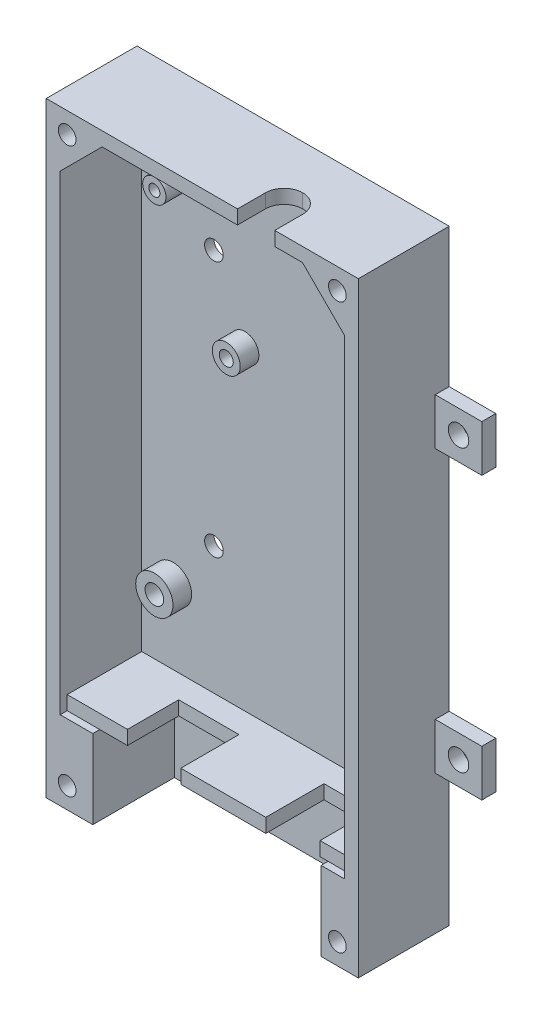
SolidWorks part; units mm, degrees
ref_plane "Front Plane" through (0, 0, 0) normal (0, 0, 1) x (1, 0, 0)
ref_plane "Top Plane" through (0, 0, 0) normal (0, 1, 0) x (1, 0, 0)
ref_plane "Right Plane" through (0, 0, 0) normal (1, 0, 0) x (0, 0, -1)
sketch "Sketch1" plane through (0, 0, 0) normal (0, 0, 1) x (1, 0, 0)
  line L9 (34.9482, -66.4467) -> (-32.0518, -66.4467)
  line L25 (-28.0518, -185.7817) -> (-28.0518, -70.4467) construction
  line L26 (30.9482, -70.4467) -> (-28.0518, -70.4467) construction
  line L27 (30.9482, -185.7817) -> (30.9482, -70.4467) construction
  line L28 (30.9482, -185.7817) -> (-28.0518, -185.7817) construction
  line L29 (15.5804, -174.6788) -> (15.5804, -176.5076)
  line L30 (24.7244, -176.5076) -> (15.5804, -176.5076)
  line L31 (24.7244, -174.6788) -> (24.7244, -176.5076)
  line L32 (24.7244, -174.6788) -> (15.5804, -174.6788)
  line L33 (-15.6108, -174.6788) -> (-15.6108, -181.0288)
  line L34 (-3.6728, -181.0288) -> (-15.6108, -181.0288)
  line L35 (-3.6728, -174.6788) -> (-3.6728, -181.0288)
  line L36 (-3.6728, -174.6788) -> (-15.6108, -174.6788)
  line L37 (-29.0518, -69.4467) -> (-29.0518, -176.5076)
  line L38 (31.9482, -176.5076) -> (-29.0518, -176.5076)
  line L39 (31.9482, -69.4467) -> (31.9482, -176.5076)
  line L40 (31.9482, -69.4467) -> (-29.0518, -69.4467)
  line L41 (31.9482, -179.5076) -> (-29.0518, -179.5076)
  line L42 (34.9482, -196.4467) -> (-32.0518, -196.4467)
  line L43 (-32.0518, -196.4467) -> (-32.0518, -66.4467)
  line L44 (34.9482, -196.4467) -> (34.9482, -66.4467)
  line L45 (31.9482, -186.7817) -> (-29.0518, -186.7817)
  line L46 (-29.0518, -186.7817) -> (-29.0518, -69.4467)
  line L47 (31.9482, -69.4467) -> (-29.0518, -69.4467)
  line L48 (31.9482, -186.7817) -> (31.9482, -69.4467)
  circle A6 centre (25.9944, -160.5564) radius 1.5621
  circle A7 centre (-22.3418, -160.5564) radius 1.5621
  circle A8 centre (-6.9003, -108.9309) radius 1.3153
  circle A9 centre (21.1159, -108.9309) radius 1.5621
  circle A10 centre (-22.3418, -85.4232) radius 1.5621
  circle A11 centre (25.9944, -77.9302) radius 1.5621
extrude "Boss-Extrude1" add sketch "Sketch1" against normal blind 2 contours L9 L43 L42 L44
sketch "Sketch2" plane through (0, 0, 0) normal (0, 0, 1) x (1, 0, 0)
  line L0 (-32.0518, -66.4467) -> (34.9482, -66.4467)
  line L22 (15.0804, -179.5076) -> (-3.1728, -179.5076)
  line L23 (15.0804, -176.5076) -> (15.0804, -179.5076)
  line L24 (-3.1728, -176.5076) -> (15.0804, -176.5076)
  line L25 (-3.1728, -179.5076) -> (-3.1728, -176.5076)
  line L26 (-32.0518, -179.5076) -> (-32.0518, -66.4467)
  line L27 (-16.1108, -179.5076) -> (-32.0518, -179.5076)
  line L28 (-16.1108, -176.5076) -> (-16.1108, -179.5076)
  line L29 (-29.0518, -176.5076) -> (-16.1108, -176.5076)
  line L30 (-29.0518, -69.4467) -> (-29.0518, -176.5076)
  line L31 (31.9482, -69.4467) -> (-29.0518, -69.4467)
  line L32 (31.9482, -176.5076) -> (31.9482, -69.4467)
  line L33 (25.2244, -176.5076) -> (31.9482, -176.5076)
  line L34 (25.2244, -179.5076) -> (25.2244, -176.5076)
  line L35 (34.9482, -179.5076) -> (25.2244, -179.5076)
  line L36 (34.9482, -66.4467) -> (34.9482, -179.5076)
extrude "Boss-Extrude2" add sketch "Sketch2" along normal blind 17.5
sketch "Sketch3" plane through (0, 0, 0) normal (0, 0, 1) x (1, 0, 0)
  circle A10 centre (-6.9003, -108.9309) radius 3
  circle A11 centre (-6.9003, -108.9309) radius 1.5
  circle A12 centre (-22.3418, -85.4232) radius 2.5
  circle A13 centre (-22.3418, -85.4232) radius 1.2
  circle A14 centre (25.9944, -77.9302) radius 2.5
  circle A15 centre (25.9944, -77.9302) radius 1.2
  circle A16 centre (25.9944, -160.5564) radius 2.5
  circle A17 centre (25.9944, -160.5564) radius 1.2
  circle A18 centre (-22.3418, -160.5564) radius 4
  circle A19 centre (-22.3418, -160.5564) radius 2
extrude "Boss-Extrude3" add sketch "Sketch3" along normal blind 4
sketch "Sketch4" plane through (0, 0, 0) normal (0, 0, 1) x (1, 0, 0)
  line L1 (-16.1108, -179.5076) -> (-3.1728, -179.5076)
  line L2 (-16.1108, -179.5076) -> (-16.1108, -176.5076)
  line L3 (-16.1108, -176.5076) -> (-3.1728, -176.5076)
  line L4 (-3.1728, -179.5076) -> (-3.1728, -176.5076)
  line L5 (15.0804, -179.5076) -> (25.2244, -179.5076)
  line L6 (15.0804, -179.5076) -> (15.0804, -176.5076)
  line L7 (15.0804, -176.5076) -> (25.2244, -176.5076)
  line L8 (25.2244, -179.5076) -> (25.2244, -176.5076)
extrude "Boss-Extrude4" add sketch "Sketch4" along normal blind 5
sketch "Sketch5" plane through (0, 0, 0) normal (0, 0, 1) x (1, 0, 0)
  line L7 (-13.5518, -94.1361) -> (16.4482, -94.1361) construction
  line L8 (-13.5518, -94.1361) -> (-13.5518, -149.1361) construction
  line L9 (-13.5518, -149.1361) -> (16.4482, -149.1361) construction
  line L10 (16.4482, -94.1361) -> (16.4482, -149.1361) construction
  line L11 (31.9482, -69.4467) -> (31.9482, -176.5076) construction
  circle A4 centre (-13.5518, -94.1361) radius 2
  circle A5 centre (16.4482, -94.1361) radius 2
  circle A6 centre (-13.5518, -149.1361) radius 2
  circle A7 centre (16.4482, -149.1361) radius 2
  point P1 (16.4482, -121.6361)
  dimension "D1" = 15.5
extrude "Cut-Extrude1" cut sketch "Sketch5" against normal through all
sketch "Sketch6" plane through (0, 0, 17.5) normal (0, 0, 1) x (1, 0, 0)
  line L1 (-16.1108, -179.5076) -> (-29.0518, -179.5076)
  line L2 (-16.1108, -179.5076) -> (-16.1108, -176.5076)
  line L3 (-16.1108, -176.5076) -> (-29.0518, -176.5076)
  line L4 (-29.0518, -179.5076) -> (-29.0518, -176.5076)
extrude "Cut-Extrude2" cut sketch "Sketch6" against normal blind 1.5
sketch "Sketch7" plane through (0, 0, 0) normal (0, 0, 1) x (1, 0, 0)
  line L0 (-32.0518, -179.5076) -> (-32.0518, -196.4467)
  line L1 (-32.0518, -196.4467) -> (-22.0518, -196.4467)
  line L2 (34.9482, -196.4467) -> (-32.0518, -196.4467) construction
  line L3 (-22.0518, -196.4467) -> (-22.0518, -179.5076)
  line L4 (-32.0518, -179.5076) -> (34.9482, -179.5076) construction
  line L5 (-22.0518, -179.5076) -> (-32.0518, -179.5076)
  line L6 (34.9482, -179.5076) -> (34.9482, -196.4467)
  line L7 (34.9482, -196.4467) -> (26.9482, -196.4467)
  line L8 (26.9482, -196.4467) -> (26.9482, -179.5076)
  line L9 (26.9482, -179.5076) -> (34.9482, -179.5076)
extrude "Boss-Extrude5" add sketch "Sketch7" along normal blind 17.5
sketch "Sketch8" plane through (0, 0, 17.5) normal (0, 0, 1) x (1, 0, 0)
  line L1 (25.2244, -176.5076) -> (31.9482, -176.5076)
  line L2 (25.2244, -176.5076) -> (25.2244, -179.5076)
  line L3 (25.2244, -179.5076) -> (31.9482, -179.5076)
  line L4 (31.9482, -176.5076) -> (31.9482, -179.5076)
extrude "Cut-Extrude3" cut sketch "Sketch8" against normal blind 1.5
chamfer "Chamfer1" distance 9 angle 45 2 edges at (31.9482, -69.4467, 8.75) (-29.0518, -69.4467, 8.75)
sketch "Sketch10" plane through (0, 0, 17.5) normal (0, 0, 1) x (1, 0, 0)
  line L0 (34.9482, -66.4467) -> (-32.0518, -66.4467) construction
  line L1 (-32.0518, -196.4467) -> (-22.0518, -196.4467) construction
  line L2 (-32.0518, -66.4467) -> (-32.0518, -196.4467) construction
  line L3 (-20.0518, -69.4467) -> (22.9482, -69.4467) construction
  line L4 (1.4482, -69.4467) -> (1.4482, -66.4467) construction
  circle A0 centre (-27.5518, -70.9467) radius 1.9
  circle A1 centre (30.4482, -70.9467) radius 1.9
  circle A2 centre (-27.5518, -191.9467) radius 1.9
  circle A3 centre (30.4482, -191.9467) radius 1.9
  dimension "D1" = 4.5
  dimension "D3" = 4.5
  dimension "D2" = 4.5
extrude "Cut-Extrude4" cut sketch "Sketch10" against normal through all
sketch "Sketch11" plane through (0, 0, 0) normal (0, 0, 1) x (1, 0, 0)
  circle A0 centre (-22.3418, -160.5564) radius 2
extrude "Cut-Extrude5" cut sketch "Sketch11" against normal through all
sketch "Sketch13" plane through (0, 0, 17.5) normal (0, 0, 1) x (1, 0, 0)
  line L5 (-20.0518, -69.4467) -> (22.9482, -69.4467) construction
  line L6 (9.0074, -69.4467) -> (17.0074, -69.4467)
  line L7 (9.0074, -69.4467) -> (9.0074, -66.4467)
  line L8 (9.0074, -66.4467) -> (17.0074, -66.4467)
  line L9 (17.0074, -69.4467) -> (17.0074, -66.4467)
  line L10 (34.9482, -66.4467) -> (-32.0518, -66.4467) construction
extrude "Cut-Extrude6" cut sketch "Sketch13" against normal blind 10 contours L7 L8 L9 L6
fillet "Fillet1" radius 4 2 edges at (17.0074, -67.9467, 7.5) (9.0074, -67.9467, 7.5)
sketch "Sketch14" plane through (0, 0, -2) normal (0, 0, -1) x (-1, 0, 0)
  line L0 (32.0518, -96.2685) -> (42.0518, -96.2685)
  line L1 (32.0518, -196.4467) -> (32.0518, -66.4467) construction
  line L2 (42.0518, -96.2685) -> (42.0518, -106.2685)
  line L3 (42.0518, -106.2685) -> (32.0518, -106.2685)
  line L4 (32.0518, -96.2685) -> (32.0518, -106.2685)
  line L5 (-1.4482, -66.4467) -> (-1.4482, -196.4467) construction
  line L6 (-34.9482, -66.4467) -> (32.0518, -66.4467) construction
  line L7 (-34.9482, -196.4467) -> (32.0518, -196.4467) construction
  line L8 (-34.9482, -131.4467) -> (32.0518, -131.4467) construction
  line L9 (-34.9482, -196.4467) -> (-34.9482, -66.4467) construction
  line L10 (-34.9482, -96.2685) -> (-34.9482, -106.2685)
  line L11 (-44.9482, -106.2685) -> (-34.9482, -106.2685)
  line L12 (-44.9482, -96.2685) -> (-44.9482, -106.2685)
  line L13 (-34.9482, -96.2685) -> (-44.9482, -96.2685)
  line L14 (-34.9482, -166.6248) -> (-44.9482, -166.6248)
  line L15 (-44.9482, -166.6248) -> (-44.9482, -156.6248)
  line L16 (-44.9482, -156.6248) -> (-34.9482, -156.6248)
  line L17 (-34.9482, -166.6248) -> (-34.9482, -156.6248)
  line L18 (32.0518, -166.6248) -> (32.0518, -156.6248)
  line L19 (42.0518, -156.6248) -> (32.0518, -156.6248)
  line L20 (42.0518, -166.6248) -> (42.0518, -156.6248)
  line L21 (32.0518, -166.6248) -> (42.0518, -166.6248)
  circle A0 centre (37.0518, -101.2685) radius 2.2
  circle A1 centre (-39.9482, -101.2685) radius 2.2
  circle A2 centre (-39.9482, -161.6248) radius 2.2
  circle A3 centre (37.0518, -161.6248) radius 2.2
  point P36 (37.0518, -161.6248)
  point P37 (37.0518, -101.2685)
  point P38 (-39.9482, -101.2685)
  point P39 (-39.9482, -161.6248)
extrude "Boss-Extrude6" add sketch "Sketch14" against normal blind 3
sketch "Sketch15" plane through (0, 0, 0) normal (0, 0, 1) x (1, 0, 0)
  circle A0 centre (-22.3418, -85.4232) radius 1.2
  circle A1 centre (25.9944, -77.9302) radius 1.2
  circle A2 centre (-6.9003, -108.9309) radius 1.5
  circle A3 centre (25.9944, -160.5564) radius 1.2
extrude "Cut-Extrude7" cut sketch "Sketch15" against normal through all
